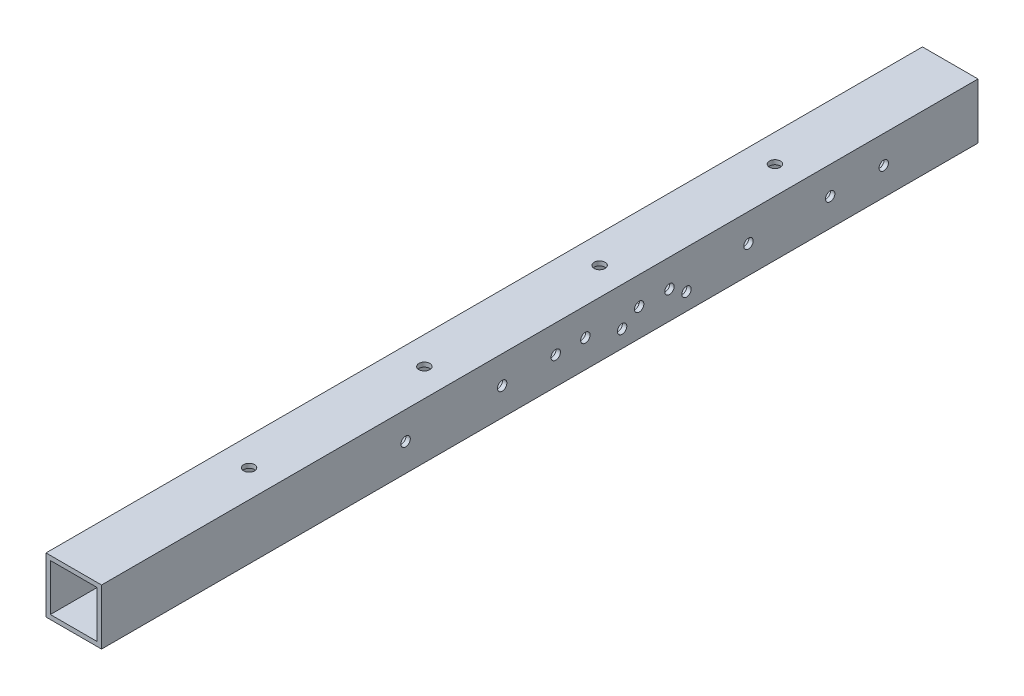
SolidWorks part; units mm, degrees
ref_plane "前基準面" through (0, 0, 0) normal (0, 0, 1) x (1, 0, 0)
ref_plane "上基準面" through (0, 0, 0) normal (0, 1, 0) x (1, 0, 0)
ref_plane "右基準面" through (0, 0, 0) normal (1, 0, 0) x (0, 0, -1)
sketch "草圖1" plane through (0, 0, 0) normal (0, 0, 1) x (1, 0, 0)
  line L0 (-10.7, 10.7) -> (10.7, 10.7)
  line L1 (-12.7, 12.7) -> (12.7, 12.7)
  line L2 (-12.7, 12.7) -> (-12.7, -12.7)
  line L3 (-12.7, -12.7) -> (12.7, -12.7)
  line L4 (12.7, 12.7) -> (12.7, -12.7)
  line L5 (-12.7, 12.7) -> (12.7, -12.7) construction
  line L6 (-12.7, -12.7) -> (12.7, 12.7) construction
  line L7 (10.7, 10.7) -> (10.7, -10.7)
  line L8 (-10.7, -10.7) -> (10.7, -10.7)
  line L9 (-10.7, 10.7) -> (-10.7, -10.7)
  point P0 (0, 0)
  dimension "D1" = 25.4
  dimension "D2" = 25.4
  dimension "D3" = 2
extrude "填料-伸長1" add sketch "草圖1" along normal blind 400.8 contours L1 L4 L3 L2
extrude "除料-伸長1" cut sketch "草圖1<3>" along normal through all contours L0 L7 L8 L9
sketch "草圖1<3>" plane through (0, 0, 0) normal (0, 0, 1) x (1, 0, 0) same geometry as "草圖1"
sketch "草圖2" plane through (12.7, 0, 0) normal (1, 0, 0) x (0, 0, -1)
  circle A0 centre (-43.1, 0) radius 2.15
  circle A1 centre (-67.6, 0) radius 2.15
extrude "除料-伸長2" cut sketch "草圖2" against normal blind 3
sketch "草圖3" plane through (0, -12.7, 0) normal (0, -1, 0) x (1, 0, 0)
  circle A0 centre (0, 43.1) radius 2.15
  circle A1 centre (0, 67.6) radius 2.15
extrude "除料-伸長3" cut sketch "草圖3" against normal blind 3
sketch "草圖4" plane through (12.7, 0, 0) normal (1, 0, 0) x (0, 0, -1)
  circle A0 centre (-104.95, 0) radius 2.15
extrude "除料-伸長4" cut sketch "草圖4" against normal blind 3
sketch "草圖5" plane through (0, -12.7, 0) normal (0, -1, 0) x (1, 0, 0)
  circle A0 centre (0, 104.95) radius 2.15
extrude "除料-伸長5" cut sketch "草圖5" against normal blind 5
sketch "草圖6" plane through (12.7, 0, 0) normal (1, 0, 0) x (0, 0, -1)
  circle A0 centre (-141.1, 0) radius 2.15
extrude "除料-伸長6" cut sketch "草圖6" against normal blind 5
sketch "草圖7" plane through (0, -12.7, 0) normal (0, -1, 0) x (1, 0, 0)
  circle A0 centre (0, 141.1) radius 2.15
extrude "除料-伸長7" cut sketch "草圖7" against normal blind 5
sketch "草圖8" plane through (0, -12.7, 0) normal (0, -1, 0) x (1, 0, 0)
  circle A0 centre (4.9, 133.3) radius 2.15
  circle A1 centre (4.9, 162.75) radius 2.15
extrude "除料-伸長8" cut sketch "草圖8" against normal blind 5
sketch "草圖9" plane through (0, -12.7, 0) normal (0, -1, 0) x (1, 0, 0)
  circle A0 centre (0, 154.95) radius 2.15
extrude "除料-伸長9" cut sketch "草圖9" against normal blind 5
sketch "草圖10" plane through (12.7, 0, 0) normal (1, 0, 0) x (0, 0, -1)
  circle A0 centre (-154.95, 0) radius 2.15
extrude "除料-伸長10" cut sketch "草圖10" against normal blind 5
sketch "草圖12" plane through (12.7, 0, 0) normal (1, 0, 0) x (0, 0, -1)
  circle A0 centre (-133.3, -4.9) radius 2.15
  circle A1 centre (-162.75, -4.9) radius 2.15
extrude "除料-伸長11" cut sketch "草圖12" against normal blind 5
sketch "草圖13" plane through (12.7, 0, 0) normal (1, 0, 0) x (0, 0, -1)
  circle A0 centre (-179.55, 0) radius 2.15
  circle A1 centre (-261.75, 0) radius 2.15
extrude "除料-伸長12" cut sketch "草圖13" against normal blind 5
sketch "草圖14" plane through (12.7, 0, 0) normal (1, 0, 0) x (0, 0, -1)
  circle A0 centre (-193.1, 0) radius 2.15
  circle A1 centre (-217.6, 0) radius 2.15
extrude "除料-伸長13" cut sketch "草圖14" against normal blind 5
sketch "草圖15" plane through (0, -12.7, 0) normal (0, -1, 0) x (1, 0, 0)
  circle A0 centre (0, 193.1) radius 2.15
  circle A1 centre (0, 217.6) radius 2.15
extrude "除料-伸長14" cut sketch "草圖15" against normal blind 5
sketch "草圖16" plane through (0, 12.7, 0) normal (0, 1, 0) x (1, 0, 0)
  line L0 (0, 0) -> (0, -80.16) construction
  line L1 (0, -80.16) -> (0, -160.32) construction
  line L2 (0, -160.32) -> (0, -240.48) construction
  line L3 (0, -240.48) -> (0, -320.64) construction
  circle A0 centre (0, -240.48) radius 2.5
  circle A1 centre (0, -320.64) radius 2.5
  circle A2 centre (0, -160.32) radius 2.5
  circle A3 centre (0, -80.16) radius 2.5
  dimension "D5" = 5
  dimension "D6" = 5
  dimension "D7" = 5
  dimension "D8" = 5
  dimension "D1" = 80.16
  dimension "D2" = 80.16
  dimension "D3" = 80.16
  dimension "D4" = 80.16
extrude "除料-伸長15" cut sketch "草圖16" against normal blind 10
sketch "草圖17" plane through (-12.7, 0, 0) normal (-1, 0, 0) x (0, 0, 1)
  line L0 (0, 0) -> (80.16, 0) construction
  line L1 (0, 12.7) -> (0, -12.7) construction
  line L2 (80.16, 0) -> (160.32, 0) construction
  line L3 (160.32, 0) -> (240.48, 0) construction
  line L4 (240.48, 0) -> (320.64, 0) construction
  circle A0 centre (80.16, 0) radius 2.5
  circle A1 centre (160.32, 0) radius 2.5
  circle A2 centre (240.48, 0) radius 2.5
  circle A3 centre (320.64, 0) radius 2.5
  dimension "D5" = 5
  dimension "D6" = 5
  dimension "D7" = 5
  dimension "D8" = 5
  dimension "D1" = 80.16
  dimension "D2" = 80.16
  dimension "D3" = 80.16
  dimension "D4" = 80.16
extrude "除料-伸長16" cut sketch "草圖17" against normal blind 10
